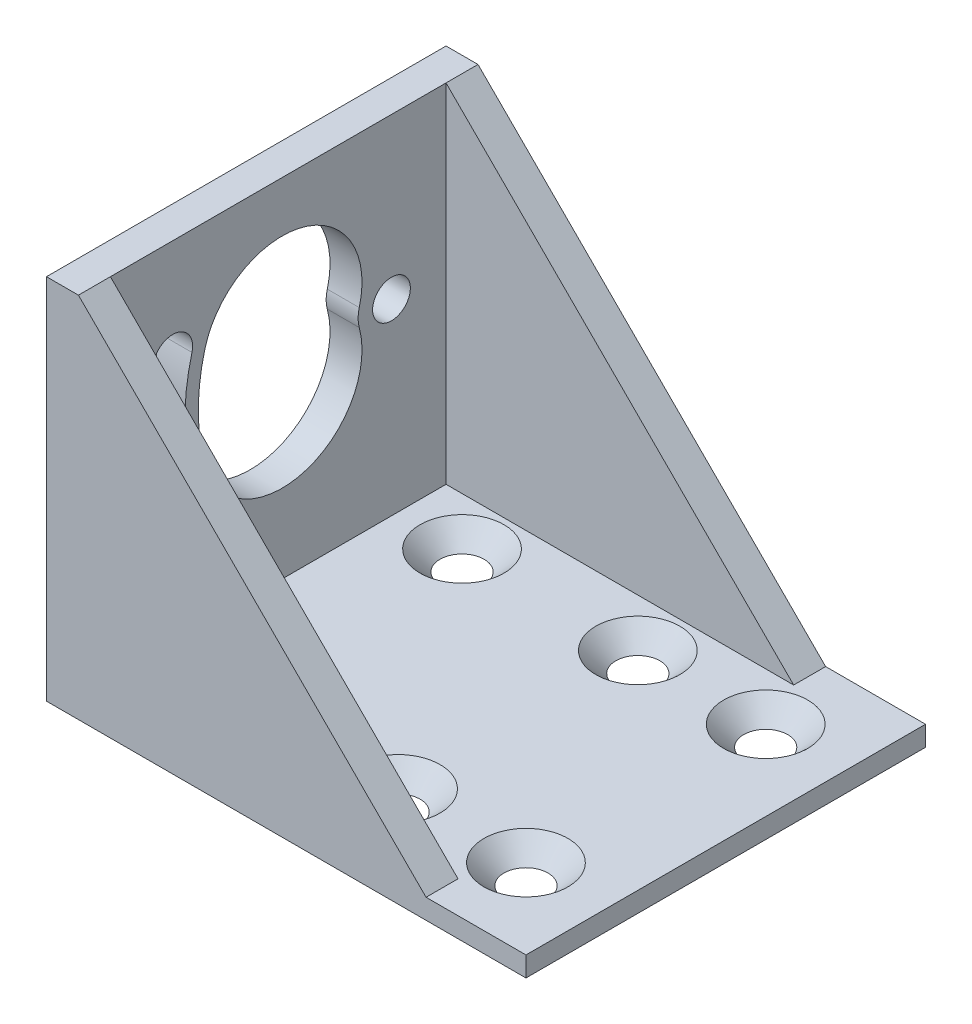
SolidWorks part; units mm, degrees
ref_plane "Front Plane" through (0, 0, 0) normal (0, 0, 1) x (1, 0, 0)
ref_plane "Top Plane" through (0, 0, 0) normal (0, 1, 0) x (1, 0, 0)
ref_plane "Right Plane" through (0, 0, 0) normal (1, 0, 0) x (0, 0, -1)
sketch "Sketch1" plane through (0, 0, 0) normal (0, 0, 1) x (1, 0, 0)
  line L0 (0, 0) -> (0, 29.21)
  line L1 (0, 29.21) -> (2.54, 29.21)
  line L2 (2.54, 29.21) -> (2.54, 1.5875)
  line L3 (2.54, 1.5875) -> (38.1, 1.5875)
  line L4 (38.1, 1.5875) -> (38.1, 0)
  line L5 (38.1, 0) -> (0, 0)
  dimension "D1" = 2.54
  dimension "D2" = 1.5875
  dimension "D3" = 38.1
  dimension "D4" = 29.21
extrude "Boss-Extrude1" add sketch "Sketch1" along normal blind 31.75
sketch "Sketch2" plane through (0, 0, 0) normal (-1, 0, 0) x (0, 0, 1)
  line L0 (31.75, 29.21) -> (31.75, 0) construction
  line L1 (31.75, 29.21) -> (0, 29.21) construction
  circle A0 centre (15.875, 16.51) radius 6.35
  dimension "D1" = 12.7
  dimension "D2" = 15.875
  dimension "D3" = 12.7
extrude "Cut-Extrude1" cut sketch "Sketch2" against normal through all
sketch "Sketch3" plane through (0, 0, 0) normal (-1, 0, 0) x (0, 0, 1)
  line L0 (6.875, 16.51) -> (24.2617, 21.1687) construction
  line L1 (6.875, 16.51) -> (24.2617, 11.8513) construction
  line L2 (6.875, 16.51) -> (15.875, 16.51) construction
  circle A0 centre (6.875, 16.51) radius 9 construction
  circle A1 centre (24.875, 16.51) radius 1.5 construction
  arc A2 (24.2617, 11.8513) -> (24.2617, 21.1687) centre (6.875, 16.51) ccw construction
  circle A3 centre (15.875, 16.51) radius 6.35 construction
  circle A4 centre (15.875, 16.51) radius 6.35 construction
  circle A5 centre (6.875, 16.51) radius 1.5 construction
  circle A6 centre (6.875, 16.51) radius 1.5
  circle A7 centre (6.875, 16.51) radius 18 construction
  arc A8 (15.5683, 18.8394) -> (15.5683, 14.1806) centre (6.875, 16.51) cw construction
  arc A9 (21.702, 12.5371) -> (21.702, 20.4829) centre (6.875, 16.51) ccw
  arc A10 (9.4347, 15.8241) -> (9.4347, 17.1959) centre (6.875, 16.51) ccw
  arc A11 (9.4347, 15.8241) -> (21.702, 12.5371) centre (15.5683, 14.1806) ccw
  arc A12 (21.702, 20.4829) -> (9.4347, 17.1959) centre (15.5683, 18.8394) ccw
  arc A13 (25.7951, 11.4404) -> (25.7951, 21.5796) centre (6.875, 16.51) ccw
  arc A14 (22.7283, 12.2621) -> (22.7283, 20.7579) centre (6.875, 16.51) ccw
  arc A15 (22.7283, 12.2621) -> (25.7951, 11.4404) centre (24.2617, 11.8513) ccw
  arc A16 (25.7951, 21.5796) -> (22.7283, 20.7579) centre (24.2617, 21.1687) ccw
  point P9 (15.875, 16.51)
  point P21 (24.875, 16.51)
  dimension "D1" = 15
  dimension "D2" = 15
  dimension "D3" = 9
  dimension "D4" = 6.35
  dimension "D5" = 1.5875
extrude "Cut-Extrude2" cut sketch "Sketch3" against normal through all
sketch "Sketch4" plane through (0, 0, 31.75) normal (0, 0, 1) x (1, 0, 0)
  line L0 (2.54, 29.21) -> (30.1625, 1.5875)
  line L1 (38.1, 1.5875) -> (2.54, 1.5875) construction
  line L2 (30.1625, 1.5875) -> (2.54, 1.5875)
  line L3 (2.54, 1.5875) -> (2.54, 29.21)
  dimension "D1" = 45
extrude "Boss-Extrude2" add sketch "Sketch4" against normal blind 2.54
extrude "Boss-Extrude3" add sketch "Sketch4<2>" against normal blind 2.54 from offset 29.21 offset against normal yes
sketch "Sketch4<2>" plane through (0, 0, 31.75) normal (0, 0, 1) x (1, 0, 0) same geometry as "Sketch4"
sketch "Sketch5" plane through (0, 1.5875, 0) normal (0, 1, 0) x (1, 0, 0)
  line L0 (30.1625, -31.75) -> (2.54, -31.75) construction
  line L1 (38.1, -31.75) -> (38.1, 0) construction
  line L2 (0, -31.75) -> (0, 0) construction
  circle A0 centre (7.62, -6.35) radius 1.75
  circle A1 centre (31.75, -25.4) radius 1.75
  circle A2 centre (31.75, -6.35) radius 1.75
  circle A3 centre (7.62, -25.4) radius 1.75
  circle A4 centre (21.59, -6.35) radius 1.75
  circle A5 centre (21.59, -25.4) radius 1.75
  point P14 (0, 0)
  point P19 (0, 0)
  point P20 (0, 0)
  point P21 (0, 0)
  dimension "D1" = 19.05
  dimension "D2" = 19.05
  dimension "D3" = 3.5
  dimension "D4" = 6.35
  dimension "D5" = 6.35
  dimension "D6" = 6.35
  dimension "D7" = 7.62
  dimension "D8" = 10.16
extrude "Cut-Extrude3" cut sketch "Sketch5" against normal blind 2.54
chamfer "Chamfer1" distance 1.5875 angle 45 6 edges at (31.75, 1.5875, 27.15) (31.75, 1.5875, 8.1) (21.59, 1.5875, 8.1) (21.59, 1.5875, 27.15) (7.62, 1.5875, 27.15) (7.62, 1.5875, 8.1)
